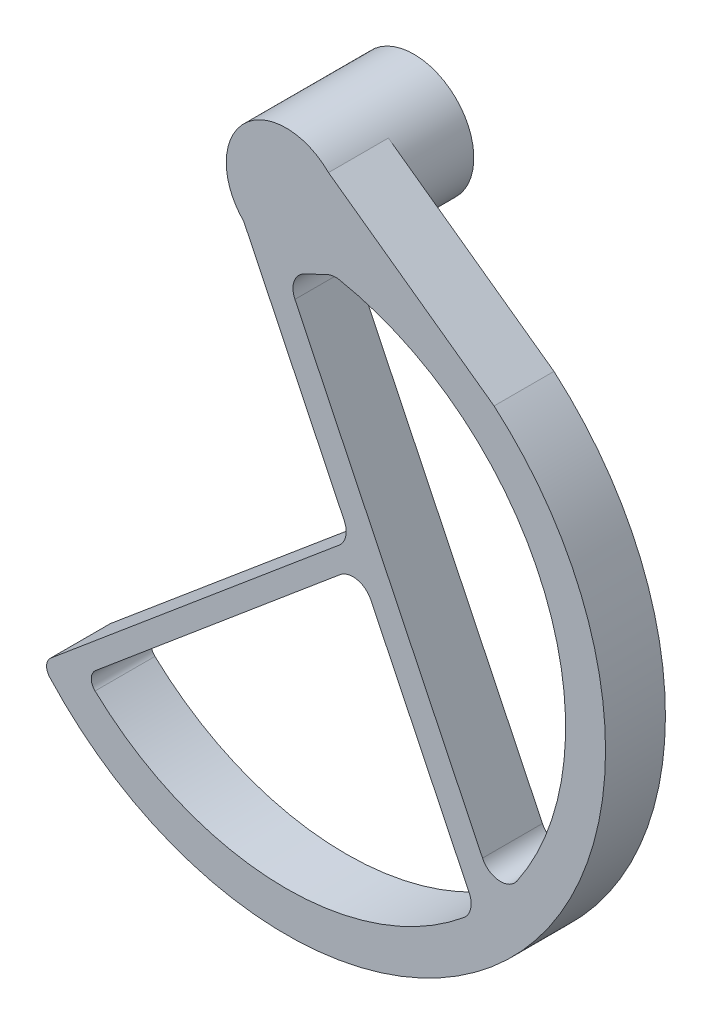
SolidWorks part; units mm, degrees
material "ABS"
ref_plane "正面" through (0, 0, 0) normal (0, 0, 1) x (1, 0, 0)
ref_plane "平面" through (0, 0, 0) normal (0, 1, 0) x (1, 0, 0)
ref_plane "右側面" through (0, 0, 0) normal (1, 0, 0) x (0, 0, -1)
sketch "ｽｹｯﾁ4" plane through (0, 0, 0) normal (0, 0, 1) x (1, 0, 0)
  line L0 (0, 0.7897) -> (0, 0)
  line L1 (-53.6231, -124.9951) -> (-58.9406, -129.4571)
  line L3 (-10.6066, -10.6066) -> (14.5363, -62.8896)
  line L4 (-53.6231, -124.9951) -> (13.2442, -68.8868)
  line L5 (21.2324, -76.8138) -> (45.8448, -127.9938)
  line L6 (10.6066, 10.6066) -> (52.0762, -19.2705)
  line L7 (-58.0696, -135.2532) -> (-57.9498, -135.1527)
  line L8 (-47.7477, -126.5866) -> (13.5112, -75.1515)
  arc A1 (-59.2335, -133.7716) -> (52.0762, -19.2705) centre (0, -80) ccw
  arc A2 (-47.8702, -131.073) -> (44.5187, -134.0193) centre (0, -80) ccw
  arc A3 (10.6066, 10.6066) -> (-10.6066, -10.6066) centre (0, 0) ccw
  arc A4 (-59.2335, -133.7716) -> (-58.9406, -129.4571) centre (-57.0123, -131.7552) cw
  arc A5 (-47.8702, -131.073) -> (-47.7477, -126.5866) centre (-45.8186, -128.8841) cw
  arc A6 (13.5112, -75.1515) -> (21.2324, -76.8138) centre (16.7264, -78.9807) cw
  arc A7 (13.2442, -68.8868) -> (14.5363, -62.8896) centre (10.0302, -65.0566) ccw
  arc A8 (45.8448, -127.9938) -> (44.5187, -134.0193) centre (41.3388, -130.1608) cw
  point P18 (-61.2836, -131.423)
  point P21 (-50.2744, -128.7081)
  point P24 (18.4421, -71.0114)
  dimension "D3" = 140
  dimension "D4" = 30
  dimension "D5" = 5
  dimension "D6" = 3
  dimension "D7" = 3
  dimension "D8" = 5
  dimension "D9" = 5
  dimension "D10" = 5
  dimension "D2" = 5
extrude "ﾎﾞｽ - 押し出し1" add sketch "ｽｹｯﾁ4" along normal blind 15 contours A7 L4 L1 A4 A1 L6 A3 L3 L5 A8 A2 A5 L8 A6 region at (29.7837, -70.5076, 0)
sketch "ｽｹｯﾁ6" plane through (0, 0, 15) normal (0, 0, 1) x (1, 0, 0)
  line L6 (49.1896, -118.7973) -> (2.2018, -21.089)
  line L7 (6.4834, -13.4819) -> (4.5408, -14.416)
  line L8 (6.4834, -13.4819) -> (10.2197, -11.6851)
  arc A0 (57.8261, -119.448) -> (13.3394, -11.2828) centre (0, -80) ccw
  arc A1 (2.2018, -21.089) -> (4.5408, -14.416) centre (6.7078, -18.9221) cw
  arc A2 (13.3394, -11.2828) -> (10.2197, -11.6851) centre (12.3866, -16.1911) ccw
  arc A3 (57.8261, -119.448) -> (49.1896, -118.7973) centre (53.6956, -116.6303) cw
  point P7 (0.0348, -16.583)
  point P14 (52.6925, -126.0814)
  dimension "D3" = 121.502
  dimension "D4" = 70
  dimension "D1" = 5
  dimension "D2" = 5
  dimension "D5" = 5
  dimension "D6" = 90
extrude "ｶｯﾄ - 押し出し1" cut sketch "ｽｹｯﾁ6" against normal blind 15
sketch "ｽｹｯﾁ11" plane through (0, 0, 0) normal (0, 0, -1) x (-1, 0, 0)
  circle A0 centre (0, 0) radius 15
extrude "ﾎﾞｽ - 押し出し3" add sketch "ｽｹｯﾁ11" along normal blind 17
sketch "ｽｹｯﾁ12" plane through (0, 0, -17) normal (0, 0, -1) x (-1, 0, 0)
  circle A0 centre (0, 0) radius 10.1
extrude "ｶｯﾄ - 押し出し5" cut sketch "ｽｹｯﾁ12" against normal blind 2
